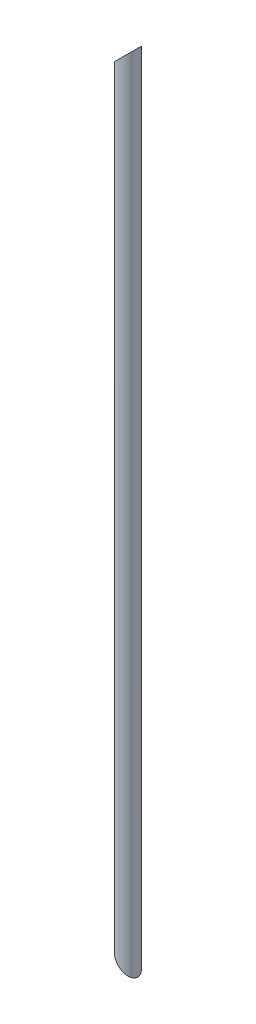
SolidWorks part; units mm, degrees
ref_plane "Plano frontal" through (0, 0, 0) normal (0, 0, 1) x (1, 0, 0)
ref_plane "Plano superior" through (0, 0, 0) normal (0, 1, 0) x (1, 0, 0)
ref_plane "Plano direito" through (0, 0, 0) normal (1, 0, 0) x (0, 0, -1)
sketch "Esboço2" plane through (0, 0, 0) normal (0, 0, 1) x (1, 0, 0)
  line L0 (0, 0) -> (0, 2650) construction
  line L1 (31.75, 0) -> (31.75, 2650)
  line L2 (31.75, 2650) -> (0, 2650)
  line L3 (31.75, 0) -> (0, 0)
  line L4 (0, 0) -> (0, 2650)
  dimension "D1" = 31.75
  dimension "D2" = 2650
revolve "Revolução2" add sketch "Esboço2" angle 360 about L0
sketch "Esboço3" plane through (0, 0, 0) normal (0, 0, 1) x (1, 0, 0)
  line L0 (-31.75, 2650) -> (31.75, 2650)
  line L1 (31.75, 2650) -> (-31.75, 2586.5)
  line L2 (-31.75, 2650) -> (-31.75, 0) construction
  line L3 (-31.75, 2586.5) -> (-31.75, 2650)
  line L4 (31.75, 0) -> (-31.75, 63.5)
  line L8 (-31.75, 63.5) -> (-31.75, 0)
  line L9 (-31.75, 0) -> (31.75, 0)
extrude "Corte-extrusão1" cut sketch "Esboço3" against normal through all both and the other way through all
sketch "Esboço9" plane through (0, 0, 0) normal (0, 1, 0) x (1, 0, 0)
  circle A0 centre (0, 0) radius 30.75
  dimension "D1" = 61.5
extrude "Corte-extrusão6" cut sketch "Esboço9" along normal through all
sketch "Esboço10" plane through (15.875, 15.875, 0) normal (-0.7071, -0.7071, 0) x (0, 0, 1)
  line L0 (0, 67.3519) -> (0, -22.4506) construction
  ellipse E0 centre (0, 22.4506) end of major axis (0, 67.3519) minor radius 31.75 construction
  point P9 (0, 22.4506)
sketch "Esboço11" plane through (0, 0, 0) normal (0, 0, 1) x (1, 0, 0)
  line L0 (0, 2618.25) -> (0, 31.75) construction
  line L1 (30.75, 2649) -> (-30.75, 2587.5) construction
  line L2 (-31.75, 63.5) -> (31.75, 0) construction
  point P6 (0, 1325)
